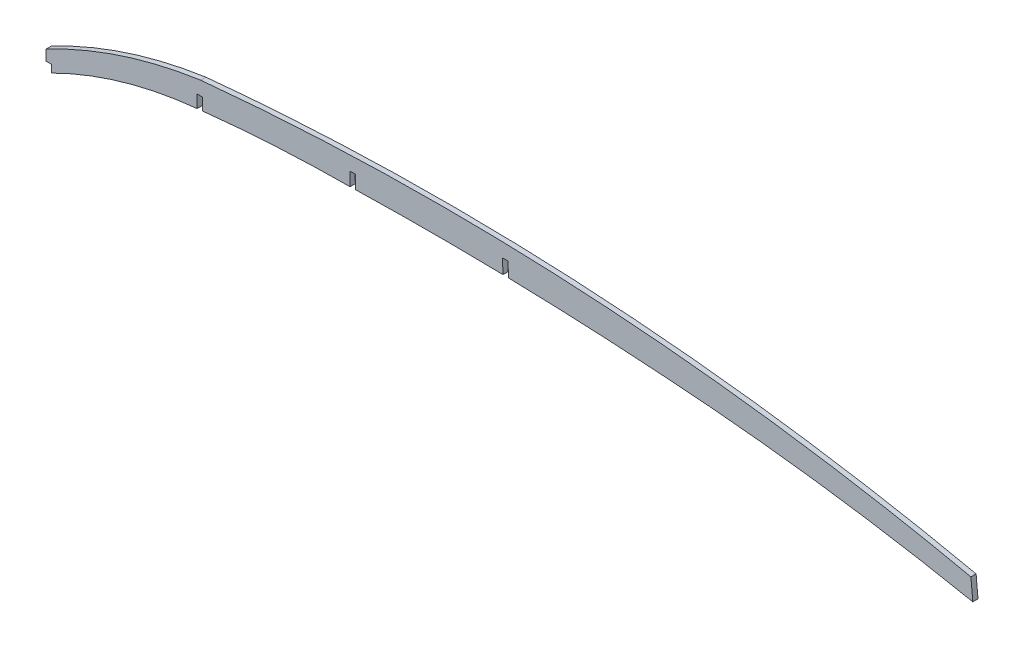
SolidWorks part; units mm, degrees
material "Plywood"
ref_plane "Front Plane" through (0, 0, 0) normal (0, 0, 1) x (1, 0, 0)
ref_plane "Top Plane" through (0, 0, 0) normal (0, 1, 0) x (1, 0, 0)
ref_plane "Right Plane" through (0, 0, 0) normal (1, 0, 0) x (0, 0, -1)
sketch "Sketch1" plane through (0, 0, 0) normal (0, 0, 1) x (1, 0, 0)
  line L0 (0, 85.9422) -> (0, 98.65)
  line L1 (566.0852, 89.3162) -> (564.9321, 101.9672)
  arc A6 (0, 85.9422) -> (92.3925, 113.3643) centre (117.1549, -139.4258) cw
  arc A7 (92.3925, 113.3643) -> (185.8959, 118.7314) centre (190.0181, -770.2591) cw
  arc A8 (0, 98.65) -> (94.4926, 129.4758) centre (136.5172, -159.5853) cw
  arc A9 (185.8959, 118.7314) -> (373.1011, 114.68) centre (236.8429, -1854.3329) cw
  arc A10 (373.1011, 114.68) -> (566.0852, 89.3162) centre (283.2319, -1315.9601) cw
  spline S6 degree 3 poles (2840.1742, -3011.9755) (2207.2857, -1054.6088) (1410.1047, -9.015) (438.4396, 123.9344) (428.6248, 125.18) (408.999, 127.4765) (399.1847, 128.5281) (369.7378, 131.3942) (350.1011, 132.9202) (291.1746, 136.3528) (251.8686, 137.1157) (-696.3591, 118.7732) (-1616.8272, -712.574) (-2553.4552, -2680.697) knots -5.888628 -5.888628 -5.888628 -5.888628 0.25 0.25 0.3125 0.3125 0.375 0.375 0.5 0.5 0.75 0.75 6.527741 6.527741 6.527741 6.527741 only from (564.9321, 101.9672) to (94.4926, 129.4758)
  spline S7 degree 3 poles (564.9321, 101.9672) (526.3055, 110.3588) (487.4057, 117.2346) (438.4396, 123.9344) (428.6248, 125.18) (408.999, 127.4765) (399.1847, 128.5281) (369.7378, 131.3942) (350.1011, 132.9202) (291.1746, 136.3528) (251.8686, 137.1157) (173.2133, 135.5942) (133.864, 133.3099) (94.4926, 129.4758) knots 0 0 0 0 0.25 0.25 0.3125 0.3125 0.375 0.375 0.5 0.5 0.75 0.75 1 1 1 1
  dimension "D4" = 92.3925
  dimension "D2" = 254
  dimension "D8" = 187.2051
  dimension "D9" = 28.7378
  dimension "D1" = 292.1
  dimension "D3" = 889
  dimension "D10" = 1973.7219
  dimension "D11" = 1433.46
  dimension "D5" = 27.4221
  dimension "D6" = 93.5034
  dimension "D7" = 32.7892
  dimension "D12" = 12.7078
extrude "Boss-Extrude1" add sketch "Sketch1" against normal mid plane 3.175 contours L1 S7 A8 L0 A6 A7 A9 A10 region at (279.3924, 119.3664, 0)
sketch "Sketch2" plane through (0, 0, 1.5875) normal (0, 0, 1) x (1, 0, 0)
  line L0 (0, 0) -> (0, 85.9422) construction
  line L1 (0, 0) -> (93.98, 0) construction
  line L3 (0, 85.9422) -> (3.302, 85.9422)
  line L4 (0, 85.9422) -> (0, 92.2922)
  line L5 (0, 92.2922) -> (3.302, 92.2922)
  line L6 (3.302, 85.9422) -> (3.302, 92.2922)
  line L7 (93.98, 0) -> (93.98, 120.9849) construction
  line L13 (187.2564, 126.8924) -> (189.9129, 0) construction
  line L14 (93.98, 0) -> (476.9285, 0) construction
  line L16 (92.2909, 121.0611) -> (95.6691, 121.0611)
  line L17 (92.2909, 121.0611) -> (92.2909, 108.3611)
  line L18 (95.6691, 121.0611) -> (95.6691, 108.3611)
  line L19 (92.2909, 108.3611) -> (95.6691, 108.3611)
  line L21 (185.5661, 126.9332) -> (188.9436, 127.0039)
  line L22 (185.5661, 126.9332) -> (185.8319, 114.236)
  line L23 (188.9436, 127.0039) -> (189.2094, 114.3067)
  line L24 (185.8319, 114.236) -> (189.2094, 114.3067)
  line L28 (278.7803, 127.5744) -> (282.1553, 127.7196)
  line L29 (278.7803, 127.5744) -> (279.3264, 114.8861)
  line L30 (280.4711, 127.5709) -> (285.9617, 0) construction
  line L31 (282.1553, 127.7196) -> (282.7014, 115.0314)
  line L32 (279.3264, 114.8861) -> (282.7014, 115.0314)
  point P8 (93.98, 108.3611)
  point P13 (187.2548, 126.9686)
  point P15 (280.4678, 127.647)
  dimension "D1" = 85.9422
  dimension "D2" = 6.35
  dimension "D3" = 3.302
  dimension "D4" = 93.98
  dimension "D5" = 88.801
  dimension "D6" = 95.9329
  dimension "D7" = 120.9849
  dimension "D8" = 0.0762
  dimension "D9" = 12.7
  dimension "D10" = 3.3782
  dimension "D11" = 126.8924
  dimension "D12" = 0.0762
  dimension "D13" = 3.3782
  dimension "D14" = 12.7
  dimension "D15" = 87.536
  dimension "D16" = 96.0488
  dimension "D17" = 127.689
  dimension "D18" = 0.0762
  dimension "D19" = 3.3782
  dimension "D20" = 12.7
extrude "Cut-Extrude1" cut sketch "Sketch2" against normal through all
equation "\"slotwidth\"=0.167708"
